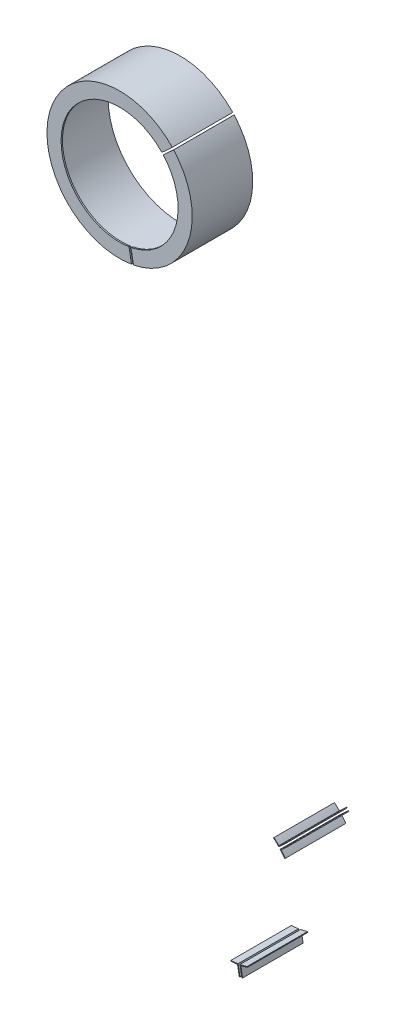
SolidWorks part; units mm, degrees
material "Alloy Steel"
ref_plane "Front Plane" through (0, 0, 0) normal (0, 0, 1) x (1, 0, 0)
ref_plane "Top Plane" through (0, 0, 0) normal (0, 1, 0) x (1, 0, 0)
ref_plane "Right Plane" through (0, 0, 0) normal (1, 0, 0) x (0, 0, -1)
sketch "Sketch1" plane through (0, 0, 0) normal (0, 0, 1) x (1, 0, 0)
  line L0 (-158.416, 821.577) -> (-79.0571, 894.8311) construction
  line L2 (-158.416, 821.577) -> (-139.1926, 715.3016) construction
  line L5 (-158.416, 821.577) -> (-54.4411, 917.5534) construction
  line L6 (-158.416, 821.577) -> (-133.2297, 682.3365) construction
  circle A0 centre (-158.416, 821.577) radius 104 construction
  circle A1 centre (-158.416, 821.577) radius 107
  circle A2 centre (-158.416, 821.577) radius 108
  dimension "D1" = 208
  dimension "D2" = 1
  dimension "D3" = 3
extrude "Boss-Extrude1" add sketch "Sketch1" along normal blind 90
sketch "Sketch5" plane through (0, 0, 90) normal (0, 0, 1) x (1, 0, 0)
  circle A0 centre (-158.416, 821.577) radius 87
  circle A1 centre (-158.416, 821.577) radius 107 construction
  circle A2 centre (-158.416, 821.577) radius 107 construction
  circle M2 centre (-158.416, 821.577) radius 107
  dimension "D1" = 20
extrude "Boss-Extrude2" add sketch "Sketch5" against normal blind 2 contours A0 M2 region at (-262.3896, 821.577, 90)
sketch "Sketch3" plane through (0, 0, 90) normal (0, 0, 1) x (1, 0, 0)
  line L0 (-80.0745, 895.9333) -> (-95.5149, 881.6806)
  line L1 (-95.5149, 881.6806) -> (-93.4801, 879.4762)
  line L2 (-93.4801, 879.4762) -> (-78.0397, 893.7289)
  line L3 (-78.0397, 893.7289) -> (-80.0745, 895.9333)
  line L4 (-144.4088, 735.712) -> (-140.6686, 715.0346)
  line L5 (-140.6686, 715.0346) -> (-137.7165, 715.5686)
  line L6 (-137.7165, 715.5686) -> (-141.4567, 736.246)
  line L7 (-141.4567, 736.246) -> (-144.4088, 735.712)
  line L8 (-142.9328, 735.979) -> (-139.1926, 715.3016)
  line L10 (-94.4975, 880.5784) -> (-79.0571, 894.8311)
  line L11 (-158.416, 821.577) -> (-139.1926, 715.3016) construction
  line L12 (-158.416, 821.577) -> (-79.0571, 894.8311) construction
  circle A0 centre (-158.416, 821.577) radius 87 construction
  circle A1 centre (-158.416, 821.577) radius 108 construction
  circle M11 centre (-158.416, 821.577) radius 108
  dimension "D1" = 3
extrude "Cut-Extrude1" cut sketch "Sketch3" against normal through all contours L10 L1 L2 | L1 L10 L0 | L10 L2 M11 | L10 L0 M11 | L10 L2 L3 M11 | L10 L3 L0 M11 | L8 L7 L4 | L7 L8 L6 | L8 L6 M11 | L8 L4 M11 | L8 L4 L5 M11 | L8 L5 L6 M11 region at (-79.8224, 895.6556, 90) region at (-87.2872, 888.2546, 90) region at (-86.2699, 887.1525, 90) region at (-78.2963, 894.0023, 90) region at (-140.3002, 715.1044, 90) region at (-141.8009, 725.5085, 90) region at (-138.0861, 715.5049, 90) region at (-140.325, 725.7755, 90)
ref_plane "Plane2" through (-482.3571, 522.5557, 0) normal (0.6783, -0.7348, 0) x (0.7348, 0.6783, 0)
ref_plane "Plane3" through (-9.4958, -1.7176, 0) normal (-0.984, -0.178, 0) x (0.178, -0.984, 0)
ref_plane "Plane4" through (231.4537, 690.9856, 0) normal (-0.3176, -0.9482, 0) x (0, 0, -1)
ref_plane "Plane5" through (0, 0, 45) normal (0, 0, 1) x (1, 0, 0)
sketch "Sketch6" plane through (0, 0, 0) normal (0, 0, 1) x (1, 0, 0)
  line L0 (78.3339, 74.3492) -> (90.0907, 85.2017)
  line L1 (90.0907, 85.2017) -> (89.4125, 85.9365)
  line L2 (89.4125, 85.9365) -> (78.377, 75.7499)
  line L3 (71.1049, 82.6141) -> (70.4526, 81.8562)
  line L4 (-80.0821, 895.9262) -> (-95.5149, 881.6806) construction
  line L5 (80.3687, 72.1448) -> (92.1256, 82.9973)
  line L6 (92.1256, 82.9973) -> (92.8038, 82.2625)
  line L7 (92.8038, 82.2625) -> (81.7684, 72.0759)
  line L8 (87.2221, 63.6891) -> (88.0298, 64.2788)
  line L10 (-93.4801, 879.4762) -> (-78.0473, 893.7218) construction
  line L12 (147.0717, 719.2503) -> (315.8357, 662.7208) construction
  line L13 (20.6976, -105.9982) -> (23.5455, -121.7427)
  line L14 (23.5455, -121.7427) -> (24.5296, -121.5647)
  line L15 (24.5296, -121.5647) -> (21.8564, -106.7862)
  line L16 (31.2616, -103.3766) -> (31.551, -104.3338)
  line L17 (19.6094, -122.4546) -> (16.9363, -107.6762)
  line L18 (20.5935, -122.2766) -> (19.6094, -122.4546)
  line L19 (17.7455, -106.5321) -> (20.5935, -122.2766)
  line L20 (6.9968, -108.7752) -> (6.9326, -107.7773)
  arc A0 (78.3339, 74.3492) -> (70.4526, 81.8562) centre (0, 0) ccw
  arc A1 (78.377, 75.7499) -> (71.1049, 82.6141) centre (0, 0) ccw
  circle A2 centre (-158.416, 821.577) radius 108 construction
  arc A3 (20.6976, -105.9982) -> (31.2616, -103.3766) centre (0, 0) ccw
  arc A4 (80.3687, 72.1448) -> (87.2221, 63.6891) centre (0, 0) cw
  arc A5 (81.7684, 72.0759) -> (88.0298, 64.2788) centre (0, 0) cw
  arc A6 (21.8564, -106.7862) -> (31.551, -104.3338) centre (0, 0) ccw
  arc A7 (16.9363, -107.6762) -> (6.9968, -108.7752) centre (0, 0) cw
  arc A8 (17.7455, -106.5321) -> (6.9326, -107.7773) centre (0, 0) cw
  dimension "D1" = 10
  dimension "D2" = 1
  dimension "D3" = 10
  dimension "D4" = 16
extrude "Boss-Extrude3" add sketch "Sketch6" along normal through all
sketch "Sketch7" plane through (-1.6957, 1.837, 0) normal (-0.6783, 0.7348, 0) x (0, 0, 1)
  line L0 (0, 123.9896) -> (0, 108.9713) construction
  line L1 (45, -102.4836) -> (45, 102.4836) construction
  circle A0 centre (24.8465, 116.4805) radius 4
  circle A2 centre (65.1535, 116.4805) radius 4
  point P4 (0, 116.4805)
  dimension "D1" = 8
extrude "Cut-Extrude2" cut sketch "Sketch7" against normal through all
mirror "Mirror4" about plane through (231.4537, 690.9856, 0) normal (-0.3176, -0.9482, 0) rebuild error yes
